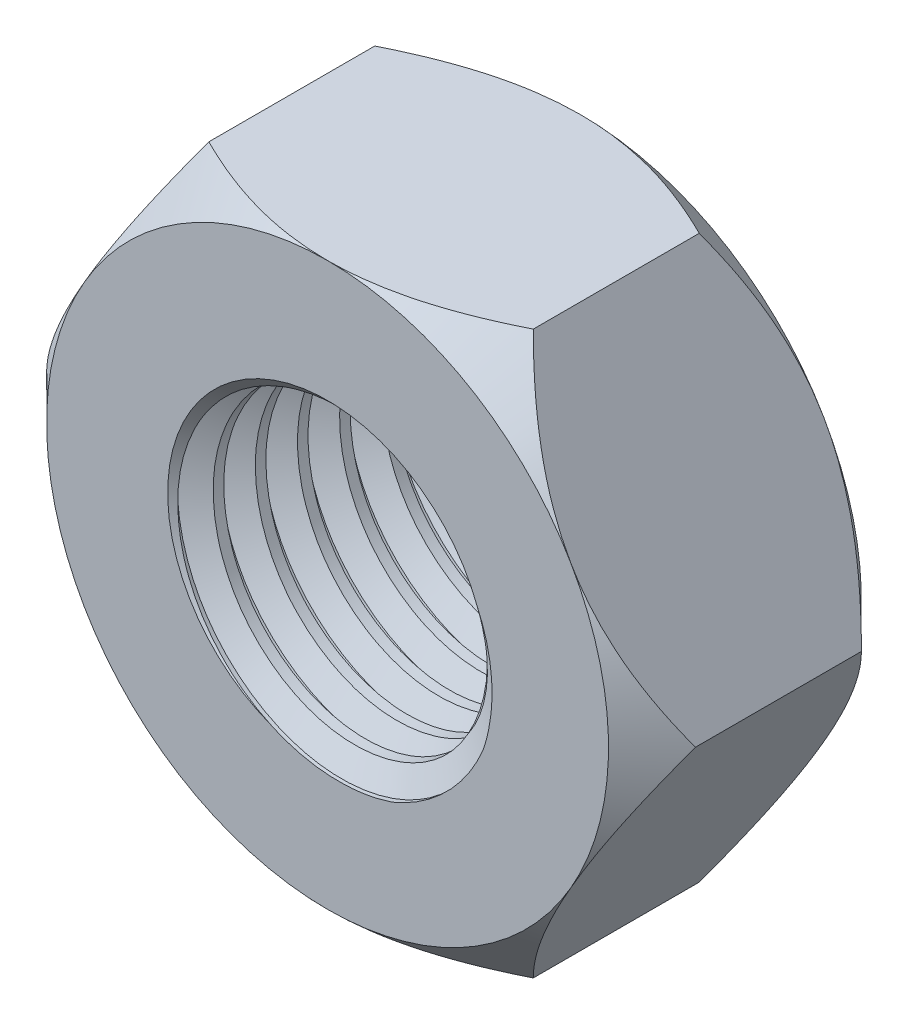
SolidWorks part; units mm, degrees
ref_plane "Front Plane" through (0, 0, 0) normal (0, 0, 1) x (1, 0, 0)
ref_plane "Top Plane" through (0, 0, 0) normal (0, 1, 0) x (1, 0, 0)
ref_plane "Right Plane" through (0, 0, 0) normal (1, 0, 0) x (0, 0, -1)
sketch "Sketch1" plane through (0, 0, 0) normal (0, 0, 1) x (1, 0, 0)
  line L1 (11.547, 0) -> (5.7735, 10)
  line L2 (5.7735, 10) -> (-5.7735, 10)
  line L3 (-5.7735, 10) -> (-11.547, 0)
  line L4 (-11.547, 0) -> (-5.7735, -10)
  line L5 (-5.7735, -10) -> (5.7735, -10)
  line L6 (5.7735, -10) -> (11.547, 0)
  circle A0 centre (0, 0) radius 10 construction
extrude "Boss-Extrude1" add sketch "Sketch1" along normal mid plane 9
sketch "Sketch2" plane through (0, 0, 4.5) normal (0, 0, 1) x (1, 0, 0)
  line L0 (-5.7735, 10) -> (-11.547, 0) construction
  circle A0 centre (0, 0) radius 10
extrude "Cut-Extrude2" cut sketch "Sketch2" against normal through all draft 45 flip side to cut
mirror "Mirror5" about plane through (0, 0, 0) normal (0, 0, 1) of "Cut-Extrude2"
sketch "Sketch3" plane through (0, 0, 4.5) normal (0, 0, 1) x (1, 0, 0)
  circle A0 centre (0, 0) radius 5.19
extrude "Cut-Extrude3" cut sketch "Sketch3" against normal through all
chamfer "Chamfer1" distance 0.5 angle 45 2 edges at (5.19, 0, -4.5) (5.19, 0, 4.5)
thread "Thread1" pitch 1.5 method cut profile "Thread Profile1" start angle 0, offset 2, length 0, pitch 1.5, diameter 10.38
ref_plane "Plane1" through (-5.19, 0, 6) normal (0, -1, 0) x (-1, 0, 0)
sketch "Thread Profile1" plane through (-5.19, 0, 6) normal (0, -1, 0) x (-1, 0, 0)
  line L0 (0, 0) -> (0, 1.5) construction
  line L1 (0, 0) -> (0.8119, 0.4687)
  line L2 (0.8119, 0.4687) -> (0.8119, 0.6562)
  line L3 (0.8119, 0.6562) -> (0, 1.125)
  line L4 (0.8119, 0.5625) -> (0, 0.5625) construction
  line L11 (0, 0) -> (0, 1.125)
  point P2 (0, 0)
  dimension "Pitch" = 1.5
  dimension "Profile_Angle" = 60
  dimension "Profile_Land" = 0.1875
  dimension "Profile_Height" = 0.8119
